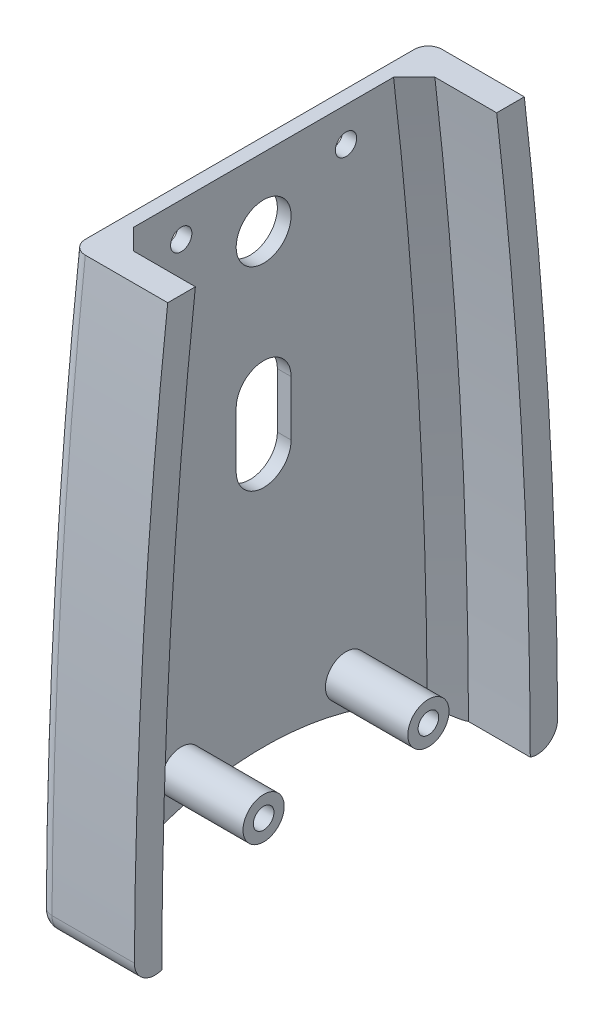
SolidWorks part; units mm, degrees
ref_plane "Front Plane" through (0, 0, 0) normal (0, 0, 1) x (1, 0, 0)
ref_plane "Top Plane" through (0, 0, 0) normal (0, 1, 0) x (1, 0, 0)
ref_plane "Right Plane" through (0, 0, 0) normal (1, 0, 0) x (0, 0, -1)
sketch "Sketch1" plane through (0, 0, 0) normal (1, 0, 0) x (0, 0, -1)
  line L0 (0, 160) -> (0, 115) construction
  line L1 (-12, 115) -> (12, 115) construction
  line L2 (-25.9681, 120) -> (25.9681, 120)
  arc A0 (-29.9652, -1.4453) -> (29.9652, -1.4453) centre (0, 0) ccw construction
  arc A1 (-19.7031, 163.4332) -> (19.7031, 163.4332) centre (0, 160) cw construction
  arc A2 (-29.9652, -1.4453) -> (-19.7031, 163.4332) centre (719.1639, 34.6875) cw construction
  arc A3 (29.9652, -1.4453) -> (19.7031, 163.4332) centre (-719.1639, 34.6875) ccw construction
  arc A4 (-29.9652, -1.4453) -> (-25.9681, 120) centre (719.1639, 34.6875) cw construction
  arc A5 (29.9652, -1.4453) -> (25.9681, 120) centre (-719.1639, 34.6875) ccw construction
  circle A8 centre (-12, 115) radius 1.55
  circle A9 centre (12, 115) radius 1.55
  arc A11 (-30.8229, 39.1246) -> (-25.9681, 120) centre (719.1639, 34.6875) cw
  arc A12 (30.8229, 39.1246) -> (25.9681, 120) centre (-719.1639, 34.6875) ccw
  arc A16 (26.0838, 36.6624) -> (-26.0838, 36.6624) centre (0, 0) ccw
  arc A17 (30.8229, 39.1246) -> (26.0838, 36.6624) centre (27.823, 39.1069) cw
  arc A18 (-26.0838, 36.6624) -> (-30.8229, 39.1246) centre (-27.823, 39.1069) cw
  point P21 (0, 115)
  point P27 (30.7803, 25.5455)
  point P28 (-30.8336, 32.7687)
  point P30 (-30.7803, 25.5455)
  dimension "D1" = 30
  dimension "D2" = 20
  dimension "D4" = 750
  dimension "D5" = 750
  dimension "D6" = 40
  dimension "D7" = 3
  dimension "D11" = 3.1
  dimension "D12" = 3
  dimension "D13" = 44.9944
  dimension "D3" = 160
  dimension "D8" = 45
  dimension "D9" = 24
extrude "Boss-Extrude1" add sketch "Sketch1" along normal blind 2
sketch "Sketch2" plane through (2, 0, 0) normal (1, 0, 0) x (0, 0, -1)
  line L14 (-15.5, 101.2) -> (15.5, 70.2) construction
  line L15 (0, 89.7) -> (0, 81.7) construction
  line L16 (4, 89.7) -> (4, 81.7)
  line L17 (-4, 89.7) -> (-4, 81.7)
  arc A8 (4, 89.7) -> (-4, 89.7) centre (0, 89.7) ccw
  arc A9 (-4, 81.7) -> (4, 81.7) centre (0, 81.7) ccw
  point P28 (0, 85.7)
  point P30 (0, 160)
  point P32 (0, 85.7)
  dimension "D11" = 160
  dimension "D12" = 74.3
  dimension "D13" = 8
  dimension "D14" = 8
extrude "Cut-Extrude1" cut sketch "Sketch2" against normal up to surface (2 mm away) up to face at (0, 115, 10.45)
sketch "Sketch3" plane through (2, 0, 0) normal (1, 0, 0) x (0, 0, -1)
  line L0 (-25.9681, 120) -> (-21.9418, 120)
  line L1 (25.9681, 120) -> (-25.9681, 120)
  line L3 (25.9681, 120) -> (21.9418, 120)
  line L5 (25.9681, 120) -> (-25.9681, 120) construction
  arc A1 (25.2669, 37.2301) -> (-25.2669, 37.2301) centre (0, 0) ccw
  arc A4 (26.0838, 36.6624) -> (30.8229, 39.1246) centre (27.823, 39.1069) ccw
  arc A6 (30.8229, 39.1246) -> (25.9681, 120) centre (-719.1639, 34.6875) ccw
  arc A7 (26.8344, 36.2744) -> (21.9418, 120) centre (-719.1639, 34.6875) ccw
  arc A20 (-26.8344, 36.2744) -> (-21.9418, 120) centre (719.1639, 34.6875) cw
  arc A21 (30.8229, 39.1246) -> (25.9681, 120) centre (-719.1639, 34.6875) ccw
  arc A22 (-25.9681, 120) -> (-30.8229, 39.1246) centre (719.1639, 34.6875) ccw
  arc A23 (-25.9681, 120) -> (-30.8229, 39.1246) centre (719.1639, 34.6875) ccw
  arc A29 (26.0838, 36.6624) -> (30.8229, 39.1246) centre (27.823, 39.1069) ccw
  arc A31 (-30.8229, 39.1246) -> (-26.0838, 36.6624) centre (-27.823, 39.1069) ccw
  arc A32 (-30.8229, 39.1246) -> (-26.0838, 36.6624) centre (-27.823, 39.1069) ccw
  arc A33 (26.0838, 36.6624) -> (-26.0838, 36.6624) centre (0, 0) ccw
  arc A34 (26.0838, 36.6624) -> (-26.0838, 36.6624) centre (0, 0) ccw
  line M29 (25.9681, 120) -> (-25.9681, 120)
  arc M45 (30.8229, 39.1246) -> (25.9681, 120) centre (-719.1639, 34.6875) ccw
  arc M46 (-25.9681, 120) -> (-30.8229, 39.1246) centre (719.1639, 34.6875) ccw
  arc M51 (-30.8229, 39.1246) -> (-26.0838, 36.6624) centre (-27.823, 39.1069) ccw
  arc M54 (26.0838, 36.6624) -> (30.8229, 39.1246) centre (27.823, 39.1069) ccw
  dimension "D2" = 746
  dimension "D3" = 746
  dimension "D1" = 0
extrude "Boss-Extrude2" add sketch "Sketch3" along normal blind 12 contours A7 M54 M45 M29 | A20 M51 M29 M46 region at (2, 78.3473, 27.1635) region at (2, 78.3473, -27.1635)
sketch "Sketch4" plane through (0, 0, 0) normal (-1, 0, 0) x (0, 0, 1)
  line L0 (-12, 48) -> (12, 48) construction
  circle A0 centre (-12, 48) radius 1.5
  circle A1 centre (12, 48) radius 1.5
  point P4 (0, 48)
  dimension "D2" = 3
  dimension "D3" = 3
  dimension "D1" = 48
  dimension "D4" = 24
extrude "Cut-Extrude2" cut sketch "Sketch4" against normal up to surface (2 mm away) up to face at (2, 115, -13.55)
sketch "草图8" plane through (2, 0, 0) normal (1, 0, 0) x (0, 0, -1)
  circle A0 centre (-12, 48) radius 3
  circle A1 centre (12, 48) radius 3
  dimension "D1" = 6
extrude "凸台-拉伸1" add sketch "草图8" along normal up to surface (12 mm away) up to face at (14, 78.625, -27.1441)
chamfer "Chamfer6" distance 3 angle 45 2 edges at (2, 78.206, -25.5656) (2, 78.206, 25.5656)
sketch "草图1" plane through (0, 0, 0) normal (-1, 0, 0) x (0, 0, 1)
  line L0 (0, 120) -> (0, 110) construction
  line L1 (-25.9681, 120) -> (25.9681, 120) construction
  line L2 (-11.9245, 113.4518) -> (11.9245, 113.4518) construction
  circle A0 centre (-12, 115) radius 1.55 construction
  circle A1 centre (12, 115) radius 1.55 construction
  circle A2 centre (0, 110) radius 4
  dimension "D1" = 8
  dimension "D2" = 10
extrude "切除-拉伸1" cut sketch "草图1" against normal blind 10
sketch "草图2" plane through (2, 0, 0) normal (1, 0, 0) x (0, 0, -1)
  line L0 (-18.9219, 120) -> (-22.1306, 85)
  line L1 (18.9219, 120) -> (22.1306, 85)
  line L2 (-22.1306, 85) -> (-8.1306, 85)
  line L3 (-18.9219, 120) -> (-8.1306, 85) construction
  line L4 (18.9219, 120) -> (8.1306, 85) construction
  line L5 (8.1306, 85) -> (22.1306, 85)
  arc A1 (-18.9219, 120) -> (-23.8279, 38.1671) centre (719.1639, 34.6875) ccw construction
  arc A3 (23.8279, 38.1671) -> (18.9219, 120) centre (-719.1639, 34.6875) ccw construction
  arc A4 (-18.9219, 120) -> (-8.1306, 85) centre (-68.1269, 85.6654) cw
  arc A5 (18.9219, 120) -> (8.1306, 85) centre (68.1269, 85.6654) ccw
  dimension "D1" = 60
  dimension "D3" = 35
  dimension "D2" = 35
  dimension "D4" = 14
ref_plane "基准面1" through (0, 120, 0) normal (0, 1, 0) x (1, 0, 0)
sketch "草图7" plane through (0, 120, -21.5938) normal (0, 1, 0) x (1, 0, 0)
  line L0 (0.0163, -48.5474) -> (0.0163, 6.2265)
  line L1 (0.0163, 6.2265) -> (14.5202, 6.2265)
  line L3 (14.5202, 6.2265) -> (14.5202, -48.5474)
  line L4 (14.5202, -48.5474) -> (0.0163, -48.5474)
sketch "草图9" plane through (0, 0, 0) normal (-1, 0, 0) x (0, 0, 1)
  circle A0 centre (-12, 48) radius 1.5
  circle A1 centre (12, 48) radius 1.5
  dimension "D1" = 3
extrude "切除-拉伸2" cut sketch "草图9" against normal through all
fillet "圆角1" radius 2 5 edges at (0, 79.6279, 29.4884) (0, 36.4447, 29.2061) (0, 44.9944, 0) (0, 36.4447, -29.2061) (0, 79.6279, -29.4884)
sketch "草图10" plane through (0, 0, 0) normal (-1, 0, 0) x (0, 0, 1)
  line L0 (-12, 48) -> (12, 48) construction
  line L1 (-1, 43.7693) -> (1, 43.7693)
  line L2 (-1, 43.7693) -> (-1, 51.156)
  line L3 (-1, 51.156) -> (1, 51.156)
  line L4 (1, 43.7693) -> (1, 51.156)
  arc A0 (27.2433, 38.292) -> (-27.2433, 38.292) centre (0, 0) ccw construction
  point P4 (0, 46.9944)
  point P5 (0, 43.7693)
  point P9 (0, 48)
  point P10 (0, 51.156)
  point P13 (0, 0)
  point P20 (-16.6753, 51.4746)
  dimension "D1" = 2
extrude "切除-拉伸3" cut sketch "草图10" against normal blind 1 contours L4 L3 L2 L1
